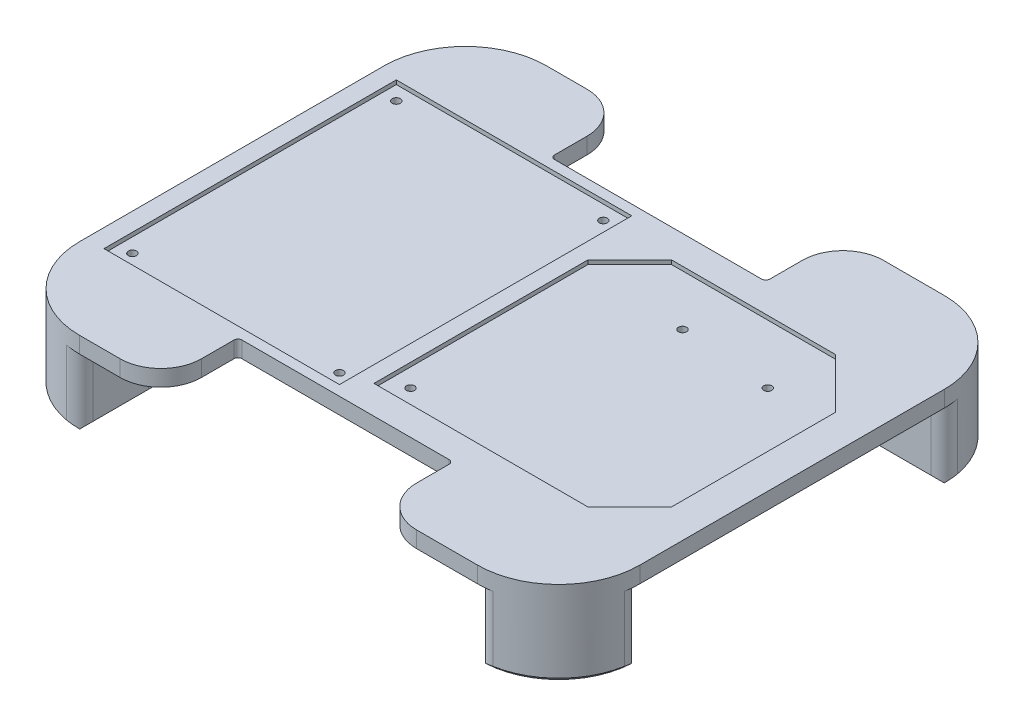
SolidWorks part; units mm, degrees
ref_plane "Plan de face" through (0, 0, 0) normal (0, 0, 1) x (1, 0, 0)
ref_plane "Plan de dessus" through (0, 0, 0) normal (0, 1, 0) x (1, 0, 0)
ref_plane "Plan de droite" through (0, 0, 0) normal (1, 0, 0) x (0, 0, -1)
sketch "Esquisse1" plane through (0, 0, 0) normal (0, 1, 0) x (1, 0, 0)
  line L0 (-26.9351, 0) -> (35.8224, 0) construction
  line L1 (0, 30.4217) -> (0, -19.2101) construction
  line L3 (-49, -57.5) -> (49, -57.5)
  line L4 (-69, -37.5) -> (-69, 37.5)
  line L5 (-49, 57.5) -> (49, 57.5)
  line L6 (69, -37.5) -> (69, 37.5)
  line L7 (-69, -57.5) -> (69, 57.5) construction
  line L8 (-69, 57.5) -> (69, -57.5) construction
  arc A0 (-69, 37.5) -> (-49, 57.5) centre (-49, 37.5) cw
  arc A1 (-49, -57.5) -> (-69, -37.5) centre (-49, -37.5) cw
  arc A2 (49, -57.5) -> (69, -37.5) centre (49, -37.5) ccw
  arc A3 (49, 57.5) -> (69, 37.5) centre (49, 37.5) cw
  point P4 (0, 0)
  dimension "D3" = 20
  dimension "D1" = 138
  dimension "D2" = 115
extrude "table" add sketch "Esquisse1" along normal blind 4
sketch "Esquisse2" plane through (0, 0, 0) normal (0, -1, 0) x (1, 0, 0)
  line L0 (-49, 57.5) -> (-49, 37.5)
  line L1 (-49, 37.5) -> (-69, 37.5)
  line L2 (-69, -37.5) -> (-49, -37.5)
  line L3 (-49, -37.5) -> (-49, -57.5)
  line L4 (49, -57.5) -> (49, -37.5)
  line L5 (49, -37.5) -> (69, -37.5)
  line L6 (49, 57.5) -> (49, 37.5)
  line L7 (49, 37.5) -> (69, 37.5)
  arc A0 (49, -57.5) -> (69, -37.5) centre (49, -37.5) ccw construction
  arc A1 (-69, -37.5) -> (-49, -57.5) centre (-49, -37.5) ccw construction
  arc A2 (-49, 57.5) -> (-69, 37.5) centre (-49, 37.5) ccw construction
  arc A3 (69, 37.5) -> (49, 57.5) centre (49, 37.5) ccw construction
  arc A4 (49, -57.5) -> (69, -37.5) centre (49, -37.5) ccw
  arc A5 (-69, -37.5) -> (-49, -57.5) centre (-49, -37.5) ccw
  arc A6 (-49, 57.5) -> (-69, 37.5) centre (-49, 37.5) ccw
  arc A7 (69, 37.5) -> (49, 57.5) centre (49, 37.5) ccw
extrude "pieds" add sketch "Esquisse2" along normal blind 17
ref_plane "limite hauteur" through (0, 34, 0) normal (0, -1, 0) x (-1, 0, 0)
sketch "Esquisse3" plane through (0, 4, 0) normal (0, 1, 0) x (1, 0, 0)
  line L0 (-64, 63.3253) -> (-64, -60.1068) construction
  line L1 (-69, 37.5) -> (-69, -37.5) construction
  line L2 (-7, 0) -> (0, 0) construction
  line L3 (-64, 35.5) -> (-7, 35.5)
  line L4 (-64, 35.5) -> (-64, -35.5)
  line L5 (-64, -35.5) -> (-7, -35.5)
  line L6 (-7, 35.5) -> (-7, -35.5)
  line L7 (-61, 32.5) -> (-10, 32.5) construction
  line L8 (-10, 32.5) -> (-10, -32.5) construction
  line L9 (-61, -32.5) -> (-10, -32.5) construction
  line L10 (-61, 32.5) -> (-61, -32.5) construction
  circle A0 centre (-61, 32.5) radius 1
  circle A1 centre (-10, 32.5) radius 1
  circle A2 centre (-10, -32.5) radius 1
  circle A3 centre (-61, -32.5) radius 1
  dimension "D5" = 2
  dimension "D1" = 5
  dimension "D2" = 57
  dimension "D3" = 71
  dimension "D4" = 3
sketch "Esquisse4" plane through (0, 4, 0) normal (0, 1, 0) x (1, 0, 0)
  line L0 (-2, 60.3786) -> (-2, -25.8929) construction
  line L1 (-7, 35.5) -> (-7, -35.5) construction
  line L2 (-2, -31) -> (-2, 31) construction
  line L3 (8, 31) -> (48, 31) construction
  line L4 (-2, 21) -> (-2, -31) construction
  line L5 (-2, -31) -> (50, -31) construction
  line L6 (60, 19) -> (60, -21) construction
  line L7 (48, 31) -> (60, 19) construction
  line L8 (60, -21) -> (50, -31) construction
  line L9 (8, 31) -> (-2, 21) construction
  line L10 (-2, 31) -> (60, 31) construction
  line L11 (60, 31) -> (60, -31) construction
  line L12 (60, -31) -> (-2, -31) construction
  line L13 (60, 0) -> (0, 0) construction
  circle A0 centre (2, -27) radius 1
  circle A1 centre (46, 17) radius 1
  circle A2 centre (23, 19) radius 1
  point P23 (0, 0)
  dimension "D10" = 2
  dimension "D1" = 5
  dimension "D2" = 10
  dimension "D3" = 12
  dimension "D4" = 45
  dimension "D5" = 10
  dimension "D6" = 45
  dimension "D7" = 62
  dimension "D8" = 45
  dimension "D9" = 62
  dimension "D11" = 4
  dimension "D12" = 4
  dimension "D13" = 14
  dimension "D14" = 14
  dimension "D15" = 37
  dimension "D16" = 12
sketch "Esquisse5" plane through (0, 4, 0) normal (0, 1, 0) x (1, 0, 0)
  line L0 (49, 57.5) -> (-49, 57.5) construction
  line L1 (-29, 57.5) -> (-24, 57.5)
  line L2 (-29, 57.5) -> (-29, 39.5)
  line L3 (-29, 39.5) -> (-24, 39.5)
  line L4 (-24, 57.5) -> (-24, 39.5)
  line L5 (-49, -57.5) -> (49, -57.5) construction
  line L6 (19, 57.5) -> (24, 57.5)
  line L7 (19, 57.5) -> (19, 39.5)
  line L8 (19, 39.5) -> (24, 39.5)
  line L9 (24, 57.5) -> (24, 39.5)
  line L10 (-29, -57.5) -> (-24, -57.5)
  line L11 (-29, -57.5) -> (-29, -39.5)
  line L12 (-29, -39.5) -> (-24, -39.5)
  line L13 (-24, -57.5) -> (-24, -39.5)
  line L14 (-26.5, 57.5) -> (-26.5, -57.5) construction
  line L15 (19, -57.5) -> (24, -57.5)
  line L16 (19, -57.5) -> (19, -39.5)
  line L17 (19, -39.5) -> (24, -39.5)
  line L18 (24, -57.5) -> (24, -39.5)
  line L19 (21.5, 57.5) -> (21.5, -57.5) construction
  line L21 (-69, 37.5) -> (-69, -37.5) construction
  line L22 (69, -37.5) -> (69, 37.5) construction
  dimension "D1" = 18
  dimension "D2" = 5
  dimension "D3" = 45
  dimension "D4" = 40
  dimension "D5" = 48
extrude "Enlèv. mat.-Extru.3" cut sketch "Esquisse5" against normal through all both and the other way through all
sketch "Esquisse6" plane through (0, 4, 0) normal (0, 1, 0) x (1, 0, 0)
  line L1 (-24, 57.5) -> (19, 57.5)
  line L2 (-24, 57.5) -> (-24, 39.5)
  line L3 (-24, 39.5) -> (19, 39.5)
  line L4 (19, 57.5) -> (19, 39.5)
  line L5 (-24, -39.5) -> (19, -39.5)
  line L6 (-24, -39.5) -> (-24, -57.5)
  line L7 (-24, -57.5) -> (19, -57.5)
  line L8 (19, -39.5) -> (19, -57.5)
extrude "Enlèv. mat.-Extru.4" cut sketch "Esquisse6" against normal through all both and the other way through all
fillet "Congé1" radius 10 4 edges at (24, 2, 57.5) (-29, 2, 57.5) (24, 2, -57.5) (-29, 2, -57.5)
chamfer "Chanfrein1" distance 1 angle 45 12 edges at (49, -17, 47.5) (63.1421, -17, 51.6421) (59, -17, 37.5) (63.1421, -17, -51.6421) (49, -17, -47.5) (59, -17, -37.5) (-63.1421, -17, -51.6421) (-59, -17, -37.5) (-49, -17, -47.5) (-63.1421, -17, 51.6421) (-49, -17, 47.5) (-59, -17, 37.5)
fillet "Congé2" radius 3 4 edges at (-49, -8, -37.5) (49, -8, -37.5) (49, -8, 37.5) (-49, -8, 37.5)
extrude "Enlèv. mat.-Extru.5" cut sketch "Esquisse3" against normal blind 18 contours A2 | A3 | A0 | A1 region at (-61, 4, -32.5) region at (-10, 4, -32.5) region at (-10, 4, 32.5) region at (-61, 4, 32.5)
extrude "Enlèv. mat.-Extru.6" cut sketch "Esquisse4" against normal through all both and the other way through all
sketch "Esquisse8" plane through (0, 4, 0) normal (0, 1, 0) x (1, 0, 0)
  line L0 (-64, -35.5) -> (-7, -35.5) construction
  line L1 (-7, 35.5) -> (-7, -35.5) construction
  line L2 (-64, 35.5) -> (-64, -35.5) construction
  line L3 (-64, 35.5) -> (-7, 35.5) construction
  line L4 (-64, -35.5) -> (-7, -35.5) construction
  line L5 (-7, 35.5) -> (-7, -35.5) construction
  line L6 (-64, 35.5) -> (-64, -35.5) construction
  line L7 (-64, 35.5) -> (-7, 35.5) construction
  line L8 (-64.5, -36) -> (-6.5, -36)
  line L9 (-6.5, 36) -> (-6.5, -36)
  line L10 (-64.5, 36) -> (-6.5, 36)
  line L11 (-64.5, 36) -> (-64.5, -36)
  dimension "D1" = 0.5
extrude "Enlèv. mat.-Extru.7" cut sketch "Esquisse8" against normal blind 1
sketch "Esquisse10" plane through (0, 4, 0) normal (0, 1, 0) x (1, 0, 0)
  line L0 (-2, -31) -> (50, -31) construction
  line L1 (60, -21) -> (50, -31) construction
  line L2 (60, 19) -> (60, -21) construction
  line L3 (48, 31) -> (60, 19) construction
  line L4 (8, 31) -> (48, 31) construction
  line L5 (8, 31) -> (-2, 21) construction
  line L6 (-2, -31) -> (50, -31) construction
  line L7 (60, -21) -> (50, -31) construction
  line L8 (60, 19) -> (60, -21) construction
  line L9 (48, 31) -> (60, 19) construction
  line L10 (8, 31) -> (48, 31) construction
  line L11 (8, 31) -> (-2, 21) construction
  line L12 (-2, 21) -> (-2, -31) construction
  line L13 (-2.5, -31.5) -> (50.2071, -31.5)
  line L14 (60.5, -21.2071) -> (50.2071, -31.5)
  line L15 (60.5, 19.2071) -> (60.5, -21.2071)
  line L16 (48.2071, 31.5) -> (60.5, 19.2071)
  line L17 (7.7929, 31.5) -> (48.2071, 31.5)
  line L18 (7.7929, 31.5) -> (-2.5, 21.2071)
  line L19 (-2.5, 21.2071) -> (-2.5, -31.5)
  dimension "D1" = 0.5
extrude "Enlèv. mat.-Extru.8" cut sketch "Esquisse10" against normal blind 1
sketch "Esquisse11" plane through (0, 4, 0) normal (0, 1, 0) x (1, 0, 0)
  line L0 (24, -39.5) -> (24, -47.5) construction
  line L1 (-29, 39.5) -> (24, 39.5)
  line L2 (-29, 39.5) -> (-29, 38.5)
  line L3 (-29, 38.5) -> (24, 38.5)
  line L4 (24, 39.5) -> (24, 38.5)
  line L5 (-29, -39.5) -> (24, -39.5)
  line L6 (-29, -39.5) -> (-29, -38.5)
  line L7 (-29, -38.5) -> (24, -38.5)
  line L8 (24, -39.5) -> (24, -38.5)
  line L9 (24, 47.5) -> (24, 39.5) construction
  dimension "D1" = 1
  dimension "D2" = 1
extrude "Enlèv. mat.-Extru.9" cut sketch "Esquisse11" against normal through all both and the other way through all
fillet "Congé3" radius 1 4 edges at (24, 2, 38.5) (-29, 2, 38.5) (24, 2, -38.5) (-29, 2, -38.5)
fillet "Congé4" radius 3 8 edges at (69, -8, 37.5) (-49, -8, -57.5) (-69, -8, -37.5) (-69, -8, 37.5) (69, -8, -37.5) (49, -8, -57.5) (49, -8, 57.5) (-49, -8, 57.5)
